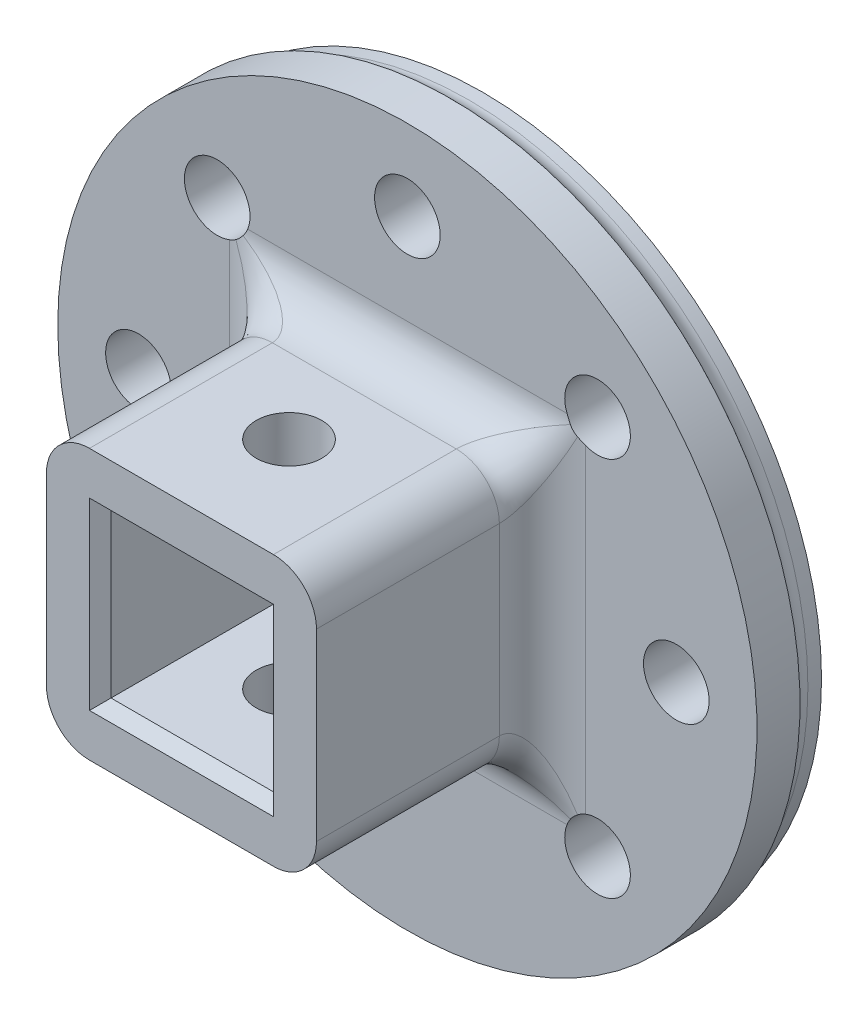
SolidWorks part; units mm, degrees
material "PLA"
ref_plane "Front Plane" through (0, 0, 0) normal (0, 0, 1) x (1, 0, 0)
ref_plane "Top Plane" through (0, 0, 0) normal (0, 1, 0) x (1, 0, 0)
ref_plane "Right Plane" through (0, 0, 0) normal (1, 0, 0) x (0, 0, -1)
sketch "Sketch1" plane through (0, 0, 0) normal (0, 0, 1) x (1, 0, 0)
  line L0 (-13.5, 0) -> (-27.8115, 0)
  line L1 (-27.8115, 0) -> (-27.8115, -5)
  line L2 (-27.8115, -5) -> (-17.8115, -5)
  line L3 (13.5, 0) -> (27.8115, 0)
  line L4 (27.8115, 0) -> (27.8115, -5)
  line L5 (27.8115, -5) -> (17.8115, -5)
  line L6 (5, -17.8115) -> (5, -32.5)
  line L7 (5, -32.5) -> (-5, -32.5)
  line L8 (-5, -32.5) -> (-5, -17.8115)
  line L9 (-13.5, 0) -> (13.5, 0) construction
  line L10 (0, 0) -> (0, -32.5) construction
  arc A0 (-13.5, 0) -> (13.5, 0) centre (0, 0) ccw
  arc A1 (-17.8115, -5) -> (-5, -17.8115) centre (0, 0) ccw
  arc A2 (5, -17.8115) -> (17.8115, -5) centre (0, 0) ccw
  dimension "D1" = 13.5
  dimension "D4" = 18.5
  dimension "D5" = 18.5
  dimension "D2" = 5
  dimension "D3" = 5
  dimension "D6" = 10
  dimension "D7" = 10
  dimension "D8" = 5
  dimension "D9" = 5
  dimension "D10" = 32.5
extrude "Boss-Extrude1" add sketch "Sketch1" along normal blind 125
sketch "Sketch2" plane through (0, 0, 0) normal (0, 0, -1) x (-1, 0, 0)
  line L2 (5, -17.8115) -> (5, -32.5) construction
  line L3 (-5, -32.5) -> (-5, -17.8115) construction
  line L4 (-5, -24.4949) -> (-5, -32.5)
  line L5 (-5, -32.5) -> (5, -32.5)
  line L6 (5, -32.5) -> (5, -24.4949)
  arc A0 (5, -24.4949) -> (-5, -24.4949) centre (0, 0) cw
  dimension "D1" = 25
extrude "Boss-Extrude2" add sketch "Sketch2" along normal blind 46
sketch "Sketch3" plane through (0, 0, -46) normal (0, 0, -1) x (-1, 0, 0)
  line L0 (0, 0) -> (0, 25) construction
  line L1 (17.6777, 17.6777) -> (0, 0) construction
  circle A0 centre (0, 0) radius 32.5
  circle A1 centre (0, 0) radius 25 construction
  circle A2 centre (0, 25) radius 3.05
  circle A3 centre (17.6777, 17.6777) radius 3.05
  circle A4 centre (25, 0) radius 3.05
  circle A5 centre (17.6777, -17.6777) radius 3.05
  circle A7 centre (-17.6777, -17.6777) radius 3.05
  circle A8 centre (-25, 0) radius 3.05
  circle A9 centre (-17.6777, 17.6777) radius 3.05
  circle A10 centre (0, -25) radius 3.05 [skipped]
  point P22 (0, 0)
  dimension "D1" = 65
  dimension "D2" = 50
  dimension "D3" = 6.1
  dimension "D5" = 45
  dimension "D4" = 8
extrude "Boss-Extrude3" add sketch "Sketch3" along normal blind 7
sketch "Sketch4" plane through (0, 0, -53) normal (0, 0, -1) x (-1, 0, 0)
  circle A0 centre (0, 0) radius 31.5
  circle A1 centre (0, 0) radius 32.5
  dimension "D1" = 63
  dimension "D2" = 65
extrude "Cut-Extrude1" cut sketch "Sketch4" against normal blind 3
fillet "Fillet1" radius 2 1 edges at (-31.5, 0, -50)
fillet "Fillet3" radius 8 5 edges at (27.8115, -2.5, 0) (-27.8115, -2.5, 0) (0, -32.5, 125) (27.8115, -2.5, 125) (-27.8115, -2.5, 125)
sketch "Sketch5" plane through (0, 0, 125) normal (0, 0, 1) x (1, 0, 0)
  line L1 (-42.5272, -35.1472) -> (42.5272, -35.1472)
  line L2 (-42.5272, -35.1472) -> (-42.5272, 35.1472)
  line L3 (-42.5272, 35.1472) -> (42.5272, 35.1472)
  line L4 (42.5272, -35.1472) -> (42.5272, 35.1472)
  line L5 (-42.5272, -35.1472) -> (42.5272, 35.1472) construction
  line L6 (-42.5272, 35.1472) -> (42.5272, -35.1472) construction
  point P1 (0, 0)
extrude "Cut-Extrude2" cut sketch "Sketch5" against normal up to surface (171 mm away) up to face at (-3.05, 25, -46)
sketch "Sketch6" plane through (0, 0, -46) normal (0, 0, 1) x (1, 0, 0)
  line L1 (-7.55, -7.55) -> (7.55, -7.55)
  line L2 (-7.55, -7.55) -> (-7.55, 7.55)
  line L3 (-7.55, 7.55) -> (7.55, 7.55)
  line L4 (7.55, -7.55) -> (7.55, 7.55)
  line L5 (-7.55, -7.55) -> (7.55, 7.55) construction
  line L6 (-7.55, 7.55) -> (7.55, -7.55) construction
  line L7 (-12.55, -12.55) -> (12.55, -12.55)
  line L8 (-12.55, -12.55) -> (-12.55, 12.55)
  line L9 (-12.55, 12.55) -> (12.55, 12.55)
  line L10 (12.55, -12.55) -> (12.55, 12.55)
  line L11 (-12.55, -12.55) -> (12.55, 12.55) construction
  line L12 (-12.55, 12.55) -> (12.55, -12.55) construction
  point P0 (0, 0)
  point P6 (0, 0)
  dimension "D1" = 15.1
  dimension "D2" = 15.1
  dimension "D3" = 25.1
  dimension "D4" = 25.1
extrude "Boss-Extrude4" add sketch "Sketch6" along normal blind 21
fillet "Fillet4" radius 4 4 edges at (0, -12.55, -46) (12.55, 0, -46) (0, 12.55, -46) (-12.55, 0, -46)
sketch "Sketch7" plane through (0, 12.55, 0) normal (0, 1, 0) x (1, 0, 0)
  line L0 (0, 25) -> (0, 35) construction
  line L1 (12.55, 25) -> (-12.55, 25) construction
  circle A0 centre (0, 35) radius 3.05
  dimension "D2" = 6.1
  dimension "D1" = 10
extrude "Cut-Extrude3" cut sketch "Sketch7" against normal through all
fillet "Fillet5" radius 4 8 edges at (-13.3786, 13.3786, -44.4376) (13.3786, 13.3786, -44.4376) (13.3786, -13.3786, -44.4376) (-13.3786, -13.3786, -44.4376) (-12.55, 12.55, -33.5) (12.55, 12.55, -33.5) (12.55, -12.55, -33.5) (-12.55, -12.55, -33.5)
chamfer "Chamfer1" distance 1 angle 45 4 edges at (7.55, 0, -25) (0, -7.55, -25) (-7.55, 0, -25) (0, 7.55, -25)
equation "\"D10@Sketch1\"=65/2"
